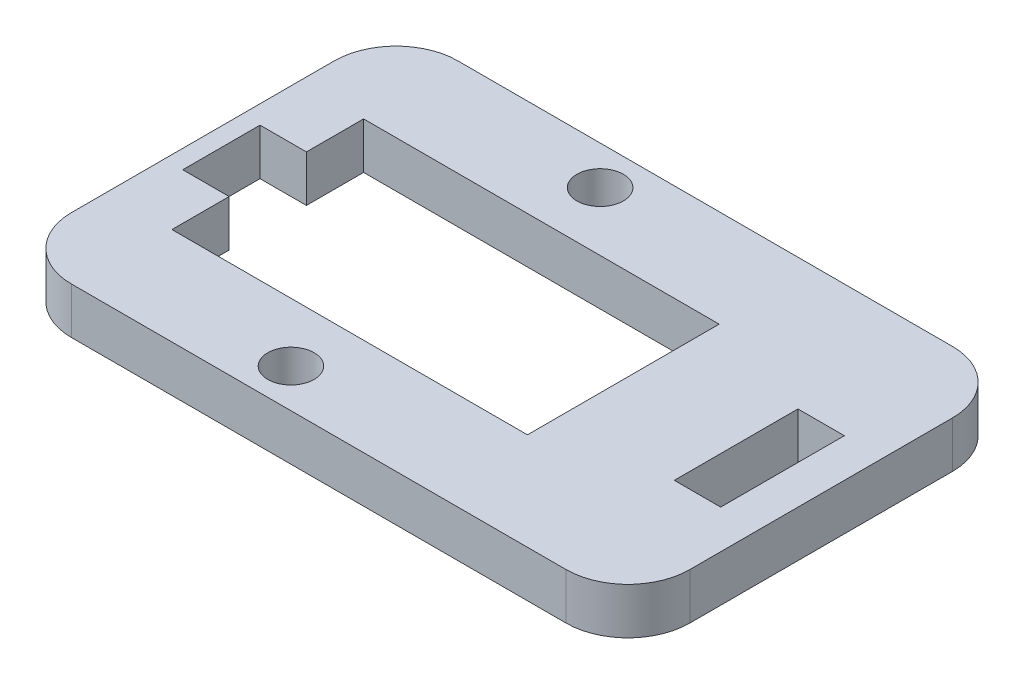
SolidWorks part; units mm, degrees
note: '?' marks a value the reader was unsure of.
material "Acrílico (médio-alto impacto)"
ref_plane "Plano frontal" through (0, 0, 0) normal (0, 0, 1) x (1, 0, 0)
ref_plane "Plano superior" through (0, 0, 0) normal (0, 1, 0) x (1, 0, 0)
ref_plane "Plano direito" through (0, 0, 0) normal (1, 0, 0) x (0, 0, -1)
sketch "Esboço1" plane through (0, 0, 0) normal (0, 1, 0) x (1, 0, 0)
  line L1 (40, 12.5) -> (0, 12.5)
  line L2 (40, 12.5) -> (40, -12.5)
  line L3 (40, -12.5) -> (0, -12.5)
  line L4 (0, 12.5) -> (0, -12.5)
  line L5 (20, -12.5) -> (20, 12.5) construction
  line L6 (40, 0) -> (0, 0) construction
  point P0 (20, 0)
  dimension "D1" = 40
  dimension "D2" = 25
sketch "Esboço7" plane through (0, 0, 0) normal (0, 1, 0) x (1, 0, 0)
  line L0 (40, 0) -> (0, 0) construction
  line L1 (37.5, 4) -> (34.5, 4)
  line L2 (37.5, 4) -> (37.5, -4)
  line L3 (37.5, -4) -> (34.5, -4)
  line L4 (34.5, 4) -> (34.5, -4)
  line L5 (36, -4) -> (36, 4) construction
  line L6 (37.5, 0) -> (34.5, 0) construction
  line L7 (40, 12.5) -> (40, -12.5) construction
  point P0 (36, 0)
  dimension "D1" = 3
  dimension "D2" = 8
  dimension "D3" = 2.5
extrude "Ressalto-extrusão1" add sketch "Esboço1" along normal blind 3
sketch "Perfil Corte" plane through (62.2239, 0, 29.7787) normal (0, -1, 0) x (-1, 0, 0)
  line L0 (46.5239, 19.7787) -> (46.5239, 39.7787) construction
  line L1 (35.0239, 23.5787) -> (58.0239, 23.5787)
  line L2 (35.0239, 23.5787) -> (35.0239, 35.9787)
  line L3 (35.0239, 35.9787) -> (58.0239, 35.9787)
  line L4 (58.0239, 23.5787) -> (58.0239, 35.9787)
  line L5 (46.5239, 35.9787) -> (46.5239, 23.5787) construction
  line L6 (35.0239, 29.7787) -> (58.0239, 29.7787) construction
  line L7 (58.0239, 29.7787) -> (62.2239, 29.7787) construction
  line L8 (62.2239, 17.2787) -> (62.2239, 42.2787) construction
  line L9 (62.2239, 42.2787) -> (22.2239, 42.2787) construction
  point P0 (46.5239, 29.7787)
  point P7 (46.5239, 29.7787)
  dimension "D1" = 23
  dimension "entre furos" = 20
  dimension "D2" = 12.4
  dimension "Afastamento Lateral" = 15.7
  dimension "Posicionamento Altura" = 12.5
sketch "Esboço6" plane through (84.444, 0, 22.6106) normal (0, -1, 0) x (-1, 0, 0)
  line L1 (80.244, 25.1106) -> (83.244, 25.1106)
  line L2 (80.244, 25.1106) -> (80.244, 20.1106)
  line L3 (80.244, 20.1106) -> (83.244, 20.1106)
  line L4 (83.244, 25.1106) -> (83.244, 20.1106)
  line L5 (81.744, 20.1106) -> (81.744, 25.1106) construction
  line L6 (80.244, 22.6106) -> (83.244, 22.6106) construction
  point P0 (81.744, 22.6106)
  dimension "D1" = 3
  dimension "D2" = 5
extrude "Corte-extrusão3" cut sketch "Esboço7" along normal through all
extrude "Corte Principal" cut sketch "Perfil Corte" against normal through all
hole_wizard "Furo de diâmetro Ø3.0 (3)1" positions "Esboço4" profile "Esboço5" hole size "Ø3.0" standard "ISO" end condition through all
sketch "Esboço4" plane through (84.444, 0, 22.6106) normal (0, -1, 0) x (-1, 0, 0)
  point P0 (68.744, 32.6106)
  point P3 (68.744, 12.6106)
sketch "Esboço5" plane through (15.7, 0, -10) normal (1, 0, 0) x (0, 0, -1)
  line L0 (0, 0) -> (0, 3)
  line L1 (0, 3) -> (1.5, 3)
  line L2 (1.5, 3) -> (1.5, 0)
  line L5 (1.5, 0) -> (0, 0)
  line L11 (0, -6.35) -> (0, 107.95) construction
  dimension "Thru Hole Dia." = 3
  dimension "Thru Hole Depth" = 3
extrude "Corte-extrusão2" cut sketch "Esboço6" against normal through all
other "Furos Motor<1>"
fillet "Filete1" radius 4 4 edges at (0, 1.5, -12.5) (40, 1.5, -12.5) (0, 1.5, 12.5) (40, 1.5, 12.5)
sketch "Esboço8" plane through (0, 0, 0) normal (0, 0, 1) x (1, 0, 0)
  line L0 (36, 3) -> (36, 0)
  line L1 (34.5, 3) -> (37.5, 3) construction
  line L2 (37.5, 0) -> (34.5, 0) construction
  line L3 (2.7, 3) -> (2.7, 0)
  line L4 (1.2, 3) -> (4.2, 3) construction
  line L5 (1.2, 0) -> (4.2, 0) construction
other "PontoR1"
other "PontoR2"
other "PontoR3"
other "PontoR4"
ref_axis "Eixo1" through (36, 3, 0) along (0, -1, 0)?
ref_axis "Eixo2" through (2.7, 3, 0) along (0, -1, 0)?
